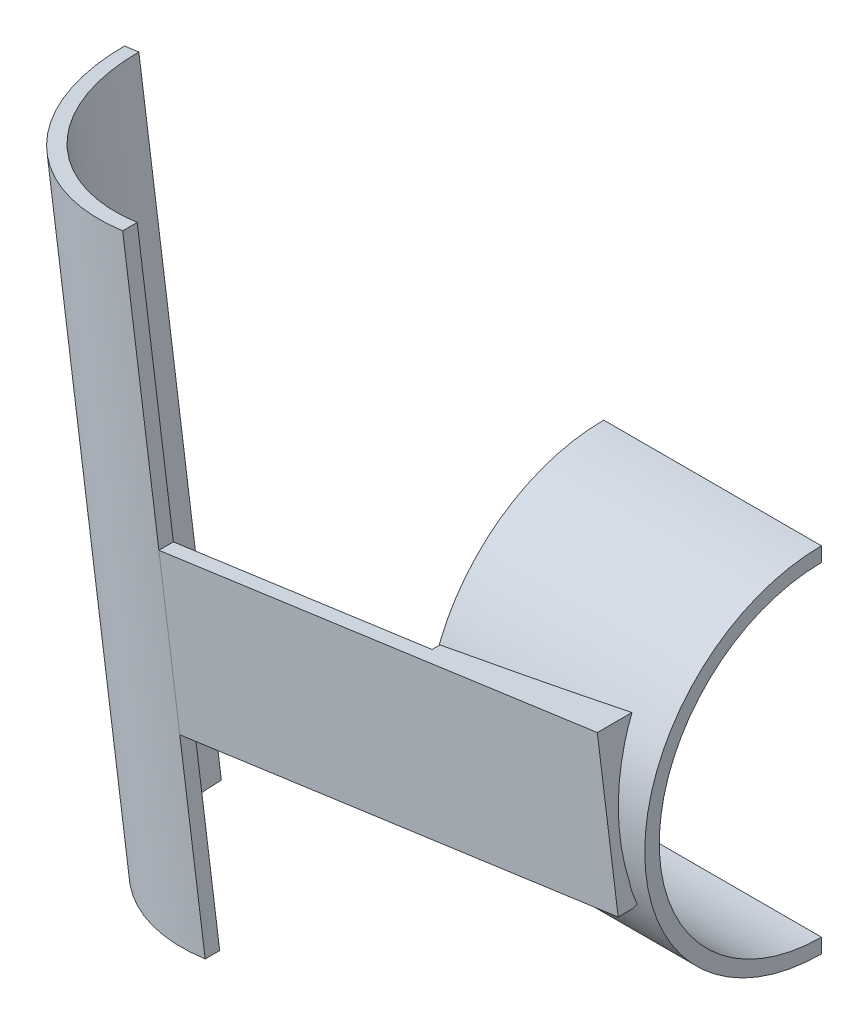
SolidWorks part; units mm, degrees
ref_plane "Front Plane" through (0, 0, 0) normal (0, 0, 1) x (1, 0, 0)
ref_plane "Top Plane" through (0, 0, 0) normal (0, 1, 0) x (1, 0, 0)
ref_plane "Right Plane" through (0, 0, 0) normal (1, 0, 0) x (0, 0, -1)
sketch "Sketch1" plane through (0, 0, 0) normal (0, 0, 1) x (1, 0, 0)
  line L0 (455.4819, 880.2488) -> (455.4819, 835.5488) construction
  line L1 (391.4041, 894.3046) -> (438.4454, 900.8896) construction
  line L2 (391.4041, 894.3046) -> (402.7935, 812.9429) construction
  line L3 (438.4454, 900.8896) -> (449.8348, 819.528) construction
  line L4 (449.8348, 819.528) -> (402.7935, 812.9429) construction
  line L5 (414.9248, 897.5971) -> (426.3141, 816.2354) construction
  line L6 (455.4819, 857.8988) -> (420.4819, 857.8988) construction
  dimension "D1" = 44.7
  dimension "D2" = 47.5
  dimension "D3" = 35
ref_plane "Plane1" through (455.4819, 0, 0) normal (1, 0, 0) x (0, 0, -1)
ref_plane "Plane2" through (-103.8709, 742.0178, 0) normal (0.1386, -0.9903, 0) x (-0.9903, -0.1386, 0)
sketch "Sketch2" plane through (455.4819, 0, 0) normal (1, 0, 0) x (0, 0, -1)
  circle A0 centre (0, 857.8988) radius 22.35
  circle A1 centre (0, 857.8988) radius 24.35
  dimension "D1" = 2
sketch "Sketch3" plane through (-103.8709, 742.0178, 0) normal (0.1386, -0.9903, 0) x (-0.9903, -0.1386, 0)
  line L0 (-559.1045, 0) -> (-511.6045, 0) construction
  circle A0 centre (-535.3545, 0) radius 23.75
  circle A1 centre (-535.3545, 0) radius 25.75
  dimension "D1" = 2
extrude "Boss-Extrude1" add sketch "Sketch3" against normal blind 82
extrude "Boss-Extrude2" add sketch "Sketch2" along normal blind 30 separate body
sketch "Sketch4" plane through (0, 0, 0) normal (0, 0, 1) x (1, 0, 0)
  line L0 (414.9248, 897.5971) -> (426.3141, 816.2354)
  line L1 (426.3141, 816.2354) -> (451.8155, 819.8052)
  line L2 (-129.7436, 738.396) -> (-77.9982, 745.6396) construction
  line L3 (451.8155, 819.8052) -> (440.4261, 901.1669)
  line L4 (414.9248, 897.5971) -> (440.4261, 901.1669)
  line L5 (451.8155, 819.8052) -> (440.4476, 901.0134) construction
extrude "Cut-Extrude1" cut sketch "Sketch4" against normal blind 30 and the other way blind 30
sketch "Sketch5" plane through (0, 0, 0) normal (0, 0, 1) x (1, 0, 0)
  line L1 (488.3236, 809.3216) -> (386.5072, 809.3216)
  line L2 (488.3236, 809.3216) -> (488.3236, 900.138)
  line L3 (488.3236, 900.138) -> (386.5072, 900.138)
  line L4 (386.5072, 809.3216) -> (386.5072, 900.138)
extrude "Cut-Extrude2" cut sketch "Sketch5" against normal blind 30
sketch "Sketch6" plane through (530.185, 74.2176, 0) normal (0.9903, 0.1386, 0) x (0, 0, -1)
  line L0 (-23.75, 749.2527) -> (-23.75, 831.2527) construction
  line L1 (-23.75, 795.2774) -> (-25.75, 795.2774)
  line L2 (-23.75, 795.2774) -> (-23.75, 774.5022)
  line L3 (-23.75, 774.5022) -> (-25.75, 774.5022)
  line L4 (-25.75, 795.2774) -> (-25.75, 774.5022)
  line L5 (-25.75, 749.2527) -> (-25.75, 831.2527) construction
extrude "Boss-Extrude3" add sketch "Sketch6" along normal blind 61
sketch "Sketch7" plane through (590.596, 82.6742, 0) normal (0.9903, 0.1386, 0) x (0, 0, -1)
  line L0 (-23.1073, 774.7056) -> (-23.75, 774.5022)
  line L1 (-23.75, 774.5022) -> (-25.75, 774.5022)
  line L2 (-25.75, 774.5022) -> (-25.75, 795.2774)
  line L3 (-25.75, 795.2774) -> (-20.5305, 795.2774)
  arc A0 (-20.5305, 795.2774) -> (-23.1073, 774.7056) centre (-0.4385, 782.3135) ccw
  ellipse E0 centre (0, 782.3111) end of major axis (-24.35, 782.3111) minor radius 24.1149 (0, 806.426) -> (0, 758.1963) ccw construction
extrude "Boss-Extrude5" add sketch "Sketch7" against normal blind 25
